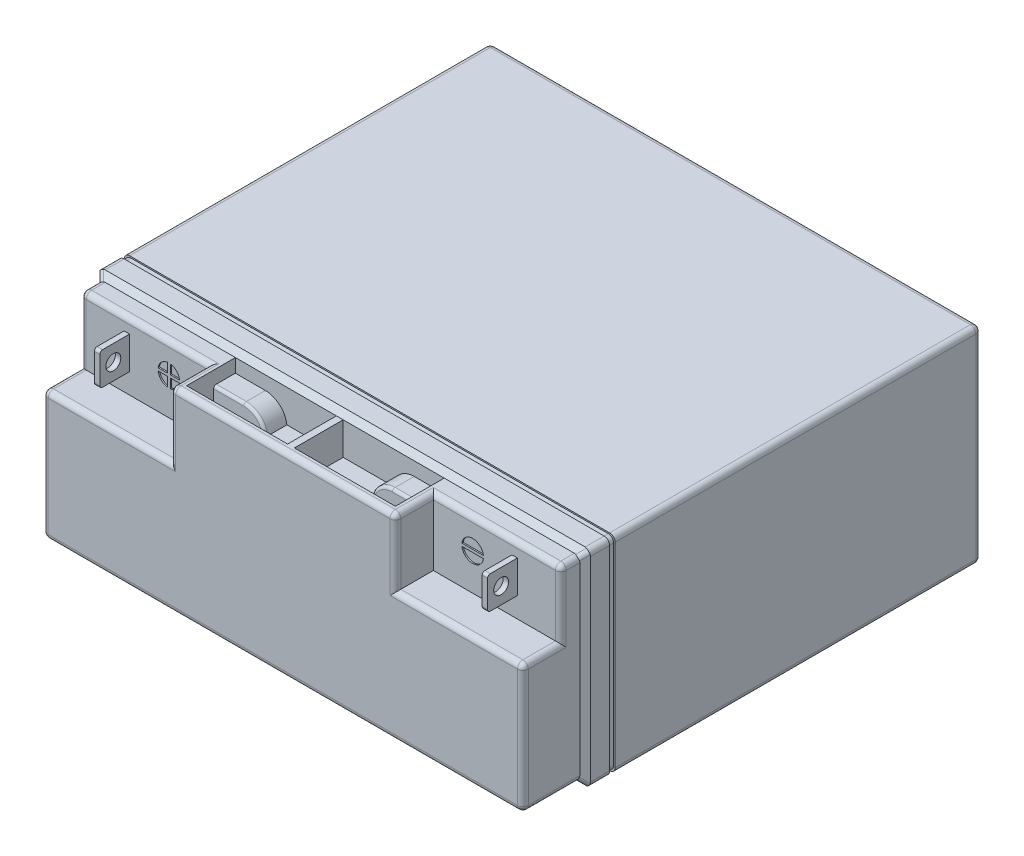
SolidWorks part; units mm, degrees
ref_plane "Front Plane" through (0, 0, 0) normal (0, 0, 1) x (1, 0, 0)
ref_plane "Top Plane" through (0, 0, 0) normal (0, 1, 0) x (1, 0, 0)
ref_plane "Right Plane" through (0, 0, 0) normal (1, 0, 0) x (0, 0, -1)
ref_plane "Plane1" through (0, 0, 0) normal (-1, 0, 0) x (0, -1, 0)
sketch "Sketch1" plane through (0, 0, 0) normal (-1, 0, 0) x (0, -1, 0)
  line L0 (-76, 144) -> (0, 144)
  line L1 (0, 144) -> (-2, 146)
  line L2 (-2, 146) -> (-74, 146)
  line L3 (-74, 146) -> (-76, 144)
extrude "Boss-Extrude1" add sketch "Sketch1" against normal blind 181
sketch "Sketch2" plane through (0, 0, 144) normal (0, 0, -1) x (-1, 0, 0)
  line L0 (-181, 76) -> (0, 76)
  line L1 (0, 76) -> (0, 0)
  line L2 (0, 0) -> (-181, 0)
  line L3 (-181, 0) -> (-181, 76)
extrude "Boss-Extrude2" add sketch "Sketch2" along normal blind 7
sketch "Sketch3" plane through (0, 0, 137) normal (0, 0, -1) x (-1, 0, 0)
  line L0 (-0.5, 0.5) -> (-180.5, 0.5)
  line L1 (-180.5, 0.5) -> (-180.5, 75.5)
  line L2 (-180.5, 75.5) -> (-0.5, 75.5)
  line L3 (-0.5, 75.5) -> (-0.5, 0.5)
extrude "Boss-Extrude3" add sketch "Sketch3" along normal blind 2
sketch "Sketch4" plane through (0, 0, 135) normal (0, 0, -1) x (-1, 0, 0)
  line L0 (-181, 75.5) -> (-0.5, 75.5)
  line L1 (-0.5, 75.5) -> (-0.5, 0.5)
  line L2 (-0.5, 0.5) -> (-181, 0.5)
  line L3 (-181, 0.5) -> (-181, 75.5)
extrude "Boss-Extrude4" add sketch "Sketch4" along normal blind 135
sketch "Sketch5" plane through (0, 75.5, 0) normal (0, 1, 0) x (-1, 0, 0)
  line L0 (-0.5, 0) -> (-181, 0)
  line L1 (-181, 0) -> (-181, 135)
  line L2 (-181, 135) -> (-0.5, 135)
  line L3 (-0.5, 135) -> (-0.5, 0)
extrude "Boss-Extrude5" add sketch "Sketch5" along normal blind 0.5
sketch "Sketch6" plane through (0, 0.5, 0) normal (0, -1, 0) x (1, 0, 0)
  line L0 (0.5, 135) -> (181, 135)
  line L1 (181, 135) -> (181, 0)
  line L2 (181, 0) -> (0.5, 0)
  line L3 (0.5, 0) -> (0.5, 135)
extrude "Boss-Extrude6" add sketch "Sketch6" along normal blind 0.5
sketch "Sketch7" plane through (0, 0, 146) normal (0, 0, 1) x (1, 0, 0)
  line L0 (52, 69) -> (63.0627, 69)
  line L1 (71, 62) -> (89.25, 62)
  line L2 (89.25, 62) -> (89.25, 74)
  line L3 (89.25, 74) -> (91.75, 74)
  line L4 (91.75, 74) -> (91.75, 62)
  line L5 (91.75, 62) -> (110, 62)
  line L6 (117.9373, 69) -> (129, 69)
  line L7 (129, 69) -> (129, 74)
  line L8 (129, 74) -> (179, 74)
  line L9 (179, 74) -> (179, 2)
  line L10 (179, 2) -> (157.75, 2)
  line L11 (157.75, 2) -> (157.75, 8)
  line L12 (157.75, 8) -> (146.6873, 8)
  line L13 (138.75, 15) -> (116.75, 15)
  line L14 (116.75, 15) -> (116.75, 2)
  line L15 (116.75, 2) -> (114.25, 2)
  line L16 (114.25, 2) -> (114.25, 15)
  line L17 (114.25, 15) -> (102, 15)
  line L18 (94, 7) -> (87, 7)
  line L19 (79, 15) -> (66.75, 15)
  line L20 (66.75, 15) -> (66.75, 2)
  line L21 (66.75, 2) -> (64.25, 2)
  line L22 (64.25, 2) -> (64.25, 15)
  line L23 (64.25, 15) -> (42.25, 15)
  line L24 (34.3127, 8) -> (23.25, 8)
  line L25 (23.25, 8) -> (23.25, 2)
  line L26 (23.25, 2) -> (2, 2)
  line L27 (2, 2) -> (2, 74)
  line L28 (2, 74) -> (52, 74)
  line L29 (52, 74) -> (52, 69)
  arc A0 (63.0627, 69) -> (71, 62) centre (63.0627, 61) cw
  arc A1 (110, 62) -> (117.9373, 69) centre (117.9373, 61) cw
  arc A2 (146.6873, 8) -> (138.75, 15) centre (146.6873, 16) cw
  arc A3 (102, 15) -> (94, 7) centre (94, 15) cw
  arc A4 (87, 7) -> (79, 15) centre (87, 15) cw
  arc A5 (42.25, 15) -> (34.3127, 8) centre (34.3127, 16) cw
extrude "Boss-Extrude7" add sketch "Sketch7" along normal blind 8
sketch "Sketch8" plane through (0, 0, 154) normal (0, 0, 1) x (1, 0, 0)
  line L0 (129, 56) -> (129, 74)
  line L1 (129, 74) -> (179, 74)
  line L2 (179, 74) -> (179, 2)
  line L3 (179, 2) -> (157.75, 2)
  line L4 (157.75, 2) -> (157.75, 21)
  line L5 (157.75, 21) -> (146.25, 21)
  line L6 (140.25, 15) -> (116.75, 15)
  line L7 (116.75, 15) -> (116.75, 2)
  line L8 (116.75, 2) -> (114.25, 2)
  line L9 (114.25, 2) -> (114.25, 15)
  line L10 (114.25, 15) -> (99.25, 15)
  line L11 (93.25, 21) -> (87.75, 21)
  line L12 (81.75, 15) -> (66.75, 15)
  line L13 (66.75, 15) -> (66.75, 2)
  line L14 (66.75, 2) -> (64.25, 2)
  line L15 (64.25, 2) -> (64.25, 15)
  line L16 (64.25, 15) -> (40.75, 15)
  line L17 (34.75, 21) -> (23.25, 21)
  line L18 (23.25, 21) -> (23.25, 2)
  line L19 (23.25, 2) -> (2, 2)
  line L20 (2, 2) -> (2, 74)
  line L21 (2, 74) -> (52, 74)
  line L22 (52, 74) -> (52, 56)
  line L23 (52, 56) -> (63.75, 56)
  line L24 (69.75, 62) -> (89.25, 62)
  line L25 (89.25, 62) -> (89.25, 74)
  line L26 (89.25, 74) -> (91.75, 74)
  line L27 (91.75, 74) -> (91.75, 62)
  line L28 (91.75, 62) -> (111.25, 62)
  line L29 (117.25, 56) -> (129, 56)
  arc A0 (146.25, 21) -> (140.25, 15) centre (146.25, 15) ccw
  arc A1 (99.25, 15) -> (93.25, 21) centre (93.25, 15) ccw
  arc A2 (87.75, 21) -> (81.75, 15) centre (87.75, 15) ccw
  arc A3 (40.75, 15) -> (34.75, 21) centre (34.75, 15) ccw
  arc A4 (63.75, 56) -> (69.75, 62) centre (63.75, 62) ccw
  arc A5 (111.25, 62) -> (117.25, 56) centre (117.25, 62) ccw
extrude "Boss-Extrude8" add sketch "Sketch8" along normal blind 10
sketch "Sketch9" plane through (0, 0, 164) normal (0, 0, 1) x (1, 0, 0)
  line L0 (2, 74) -> (179, 74)
  line L1 (179, 74) -> (179, 2)
  line L2 (179, 2) -> (2, 2)
  line L3 (2, 2) -> (2, 74)
extrude "Boss-Extrude9" add sketch "Sketch9" along normal blind 3
sketch "Sketch10" plane through (0.5, 0, 0) normal (-1, 0, 0) x (0, 0, 1)
  line L0 (0, 0) -> (0, 76)
  line L1 (0, 76) -> (135, 76)
  line L2 (135, 76) -> (135, 0)
  line L3 (135, 0) -> (0, 0)
extrude "Boss-Extrude10" add sketch "Sketch10" along normal blind 0.5
sketch "Sketch11" plane through (0, 74, 0) normal (0, 1, 0) x (-1, 0, 0)
  line L0 (-49, 153) -> (-2, 153)
  line L1 (-2, 153) -> (-2, 167)
  line L2 (-2, 167) -> (-49, 167)
  line L3 (-49, 167) -> (-49, 153)
extrude "Cut-Extrude1" cut sketch "Sketch11" against normal blind 24.5
sketch "Sketch12" plane through (0, 0, 153) normal (0, 0, 1) x (1, 0, 0)
  line L0 (18, 69) -> (20, 69)
  line L1 (20, 69) -> (20, 57)
  line L2 (20, 57) -> (18, 57)
  line L3 (18, 57) -> (18, 69)
extrude "Boss-Extrude11" add sketch "Sketch12" along normal blind 11
sketch "Sketch13" plane through (179, 0, 0) normal (1, 0, 0) x (0, 0, -1)
  line L0 (-153, 49.5) -> (-153, 74)
  line L1 (-153, 74) -> (-167, 74)
  line L2 (-167, 74) -> (-167, 49.5)
  line L3 (-167, 49.5) -> (-153, 49.5)
extrude "Cut-Extrude2" cut sketch "Sketch13" against normal blind 47
sketch "Sketch14" plane through (0, 0, 153) normal (0, 0, 1) x (1, 0, 0)
  line L0 (161, 69) -> (163, 69)
  line L1 (163, 69) -> (163, 57)
  line L2 (163, 57) -> (161, 57)
  line L3 (161, 57) -> (161, 69)
extrude "Boss-Extrude12" add sketch "Sketch14" along normal blind 11
sketch "Sketch15" plane through (0, 0, 153) normal (0, 0, 1) x (1, 0, 0)
  line L0 (34, 59.0314) -> (34, 62.5)
  line L1 (34, 62.5) -> (30.5314, 62.5)
  arc A0 (30.5314, 62.5) -> (34, 59.0314) centre (34.5, 63) ccw
extrude "Cut-Extrude3" cut sketch "Sketch15" against normal blind 0.5
sketch "Sketch16" plane through (0, 0, 153) normal (0, 0, 1) x (1, 0, 0)
  line L0 (30.5314, 63.5) -> (34, 63.5)
  line L1 (34, 63.5) -> (34, 66.9686)
  arc A0 (34, 66.9686) -> (30.5314, 63.5) centre (34.5, 63) ccw
extrude "Cut-Extrude4" cut sketch "Sketch16" against normal blind 0.5
sketch "Sketch17" plane through (0, 0, 153) normal (0, 0, 1) x (1, 0, 0)
  line L0 (38.4686, 62.5) -> (35, 62.5)
  line L1 (35, 62.5) -> (35, 59.0314)
  arc A0 (35, 59.0314) -> (38.4686, 62.5) centre (34.5, 63) ccw
extrude "Cut-Extrude5" cut sketch "Sketch17" against normal blind 0.5
sketch "Sketch18" plane through (0, 0, 153) normal (0, 0, 1) x (1, 0, 0)
  line L0 (35, 66.9686) -> (35, 63.5)
  line L1 (35, 63.5) -> (38.4686, 63.5)
  arc A0 (38.4686, 63.5) -> (35, 66.9686) centre (34.5, 63) ccw
extrude "Cut-Extrude6" cut sketch "Sketch18" against normal blind 0.5
sketch "Sketch19" plane through (0, 0, 153) normal (0, 0, 1) x (1, 0, 0)
  line L0 (150.4686, 62.5) -> (142.5314, 62.5)
  arc A0 (142.5314, 62.5) -> (150.4686, 62.5) centre (146.5, 63) ccw
extrude "Cut-Extrude7" cut sketch "Sketch19" against normal blind 0.5
sketch "Sketch20" plane through (0, 0, 153) normal (0, 0, 1) x (1, 0, 0)
  line L0 (142.5314, 63.5) -> (150.4686, 63.5)
  arc A0 (150.4686, 63.5) -> (142.5314, 63.5) centre (146.5, 63) ccw
extrude "Cut-Extrude8" cut sketch "Sketch20" against normal blind 0.5
draft "Draft1" type of draft neutral plane draft angle 45 faces to draft 1 face at (180, 38, 146) neutral plane through (179, 74, 154) neutral plane normal (1, 0, 0) parameters "D1"=45
draft "Draft2" type of draft neutral plane draft angle 45 faces to draft 1 face at (1, 38, 146) neutral plane through (2, 2, 154) neutral plane normal (-1, 0, 0) parameters "D1"=45
hole_wizard "Ø5.5 (5.5) Diameter Hole1" positions "Sketch22" profile "Sketch21" hole size "Ø5.5" standard "ANSI Metric"
sketch "Sketch22" plane through (18, 0, 0) normal (-1, 0, 0) x (0, 0, 1)
  point P0 (159, 63)
sketch "Sketch21" plane through (18, 63, 159) normal (0, 1, 0) x (0, 0, 1)
  line L0 (0, 0) -> (0, 2)
  line L1 (0, 2) -> (2.75, 2)
  line L2 (2.75, 2) -> (2.75, 0)
  line L5 (2.75, 0) -> (0, 0)
  line L11 (0, -6.35) -> (0, 107.95) construction
  dimension "Thru Hole Dia." = 5.5
  dimension "Thru Hole Depth" = 2
hole_wizard "Ø5.5 (5.5) Diameter Hole2" positions "Sketch24" profile "Sketch23" hole size "Ø5.5" standard "ANSI Metric"
sketch "Sketch24" plane through (163, 0, 0) normal (1, 0, 0) x (0, 0, -1)
  point P0 (-159, 63)
sketch "Sketch23" plane through (163, 63, 159) normal (0, 1, 0) x (0, 0, -1)
  line L0 (0, 0) -> (0, 2)
  line L1 (0, 2) -> (2.75, 2)
  line L2 (2.75, 2) -> (2.75, 0)
  line L5 (2.75, 0) -> (0, 0)
  line L11 (0, -6.35) -> (0, 107.95) construction
  dimension "Thru Hole Dia." = 5.5
  dimension "Thru Hole Depth" = 2
fillet "Fillet1" radius 1 15 edges at (112.6458, 67, 154) (123.4686, 69, 154) (162, 57, 164) (19, 57, 164) (99.6569, 9.3431, 154) (81.3431, 9.3431, 154) (90.5, 7, 154) (19, 69, 164) (152.2186, 8, 154) (141.3958, 10, 154) (162, 69, 164) (39.6042, 10, 154) (28.7814, 8, 154) (57.5314, 69, 154) (68.3542, 67, 154) tangent propagation no
fillet "Fillet2" radius 2 40 edges at (0, 0, 67.5) (90.5, 0, 0) (181, 0, 67.5) (0, 76, 67.5) (0, 38, 0) (181, 38, 0) (90.5, 76, 0) (181, 76, 67.5) (2, 49.5, 160) (2, 61.75, 153) (2, 74, 149.5) (2, 25.75, 167) (2, 2, 156.5) (90.5, 2, 167) (25.5, 49.5, 167) (25.5, 74, 153) (179, 2, 156.5) (49, 61.75, 167) (49, 74, 160) (179, 25.75, 167) (155.5, 49.5, 167) (90.5, 74, 167) (132, 61.75, 167) (179, 49.5, 160) (132, 74, 160) (179, 74, 149.5) (179, 61.75, 153) (155.5, 74, 153) (0, 0, 140.5) (181, 0, 140.5) (0, 76, 140.5) (181, 76, 140.5) (180.5, 0.5, 136) (180, 1, 145) (0.5, 0.5, 136) (1, 1, 145) (0.5, 75.5, 136) (1, 75, 145) (180.5, 75.5, 136) (180, 75, 145) tangent propagation no
fillet "Fillet3" radius 6 4 edges at (23.25, 21, 159) (52, 56, 159) (129, 56, 159) (157.75, 21, 159) tangent propagation no
